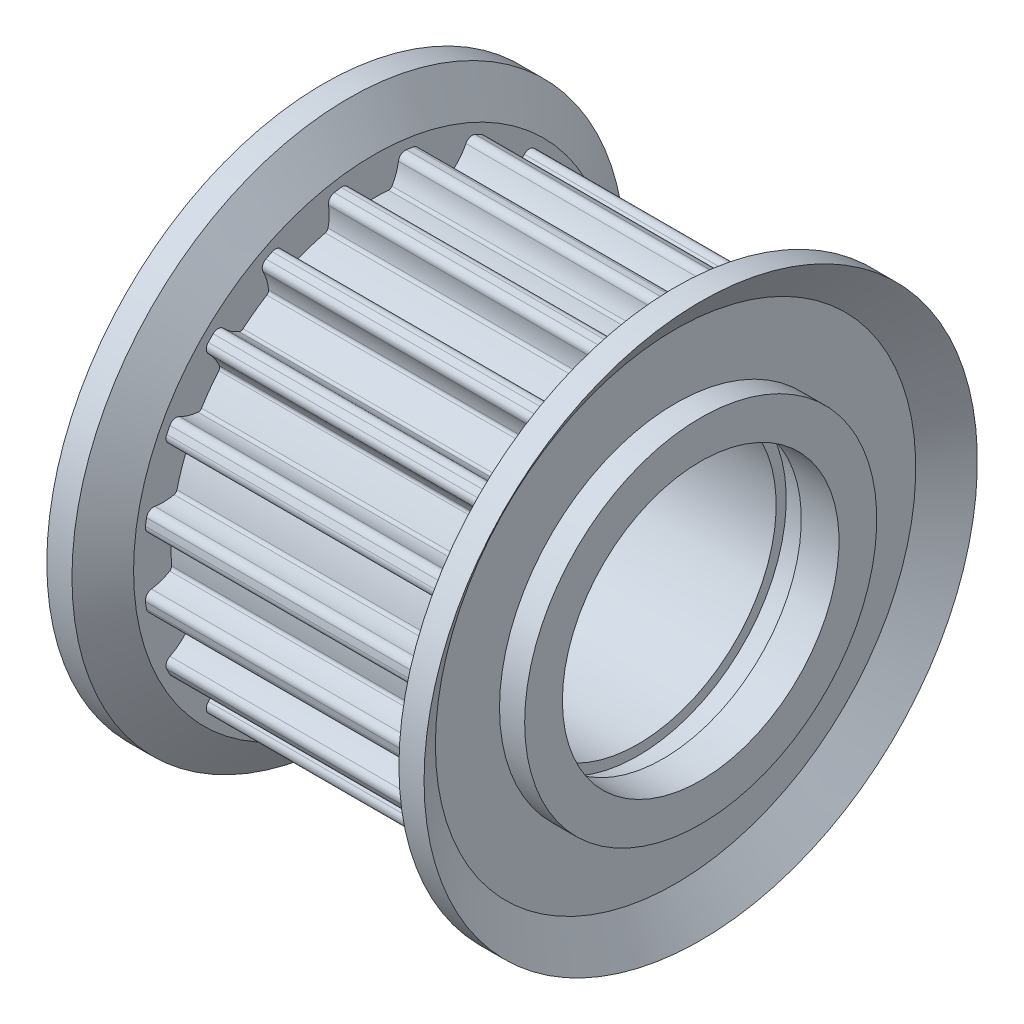
SolidWorks part; units mm, degrees
ref_plane "Front Plane" through (0, 0, 0) normal (0, 0, 1) x (1, 0, 0)
ref_plane "Top Plane" through (0, 0, 0) normal (0, 1, 0) x (1, 0, 0)
ref_plane "Right Plane" through (0, 0, 0) normal (1, 0, 0) x (0, 0, -1)
ref_plane "Plane1" through (0, 0, 0) normal (0, 0, 1) x (1, 0, 0)
sketch "Sketch1" plane through (0, 0, 0) normal (0, 0, 1) x (1, 0, 0)
  line L0 (-7.5, 4.5) -> (-5, 4.5)
  line L1 (-5, 4.5) -> (-5, 5.5)
  line L2 (-5, 5.5) -> (5, 5.5)
  line L3 (5, 5.5) -> (5, 5.9)
  line L4 (5, 5.9) -> (6, 5.9)
  line L5 (6, 5.9) -> (6, 5.5)
  line L6 (6, 5.5) -> (7.5, 5.5)
  line L7 (7.5, 5.5) -> (7.5, 7)
  line L8 (7.5, 7) -> (6.5, 7)
  line L9 (6.5, 7) -> (6.5, 9.55)
  line L10 (6.5, 9.55) -> (7.5, 11)
  line L11 (7.5, 11) -> (6.5, 11)
  line L12 (6.5, 11) -> (5.5, 9.55)
  line L13 (5.5, 9.55) -> (5.5, 9.17)
  line L14 (5.5, 9.17) -> (-5.5, 9.17)
  line L15 (-5.5, 9.17) -> (-5.5, 9.55)
  line L16 (-5.5, 9.55) -> (-6.5, 11)
  line L17 (-6.5, 11) -> (-7.5, 11)
  line L18 (-7.5, 11) -> (-6.5, 9.55)
  line L19 (-6.5, 9.55) -> (-6.5, 7)
  line L20 (-6.5, 7) -> (-7.5, 7)
  line L21 (-7.5, 7) -> (-7.5, 4.5)
  line L22 (20, 0) -> (-20, 0) construction
revolve "Revolve1" add sketch "Sketch1" angle 360 about L22 reverse direction yes
ref_plane "Plane2" through (5.5, 0, 0) normal (1, 0, 0) x (0, 0, -1)
sketch "Sketch2" plane through (5.5, 0, 0) normal (1, 0, 0) x (0, 0, -1)
  line L0 (1.2972, 9.0778) -> (1.2972, 9.8469)
  line L1 (-1.2972, 9.8469) -> (-1.2972, 9.0778)
  arc A0 (-1.2972, 9.0778) -> (-0.9803, 8.84) centre (-1.2575, 8.8006) cw
  arc A1 (-0.9803, 8.84) -> (-0.7246, 8.112) centre (0.975, 9.118) ccw
  arc A2 (-0.7246, 8.112) -> (-0.5846, 8.0388) centre (-0.5955, 8.1884) ccw
  arc A3 (-0.5846, 8.0388) -> (0.5846, 8.0388) centre (0, 0) cw
  arc A4 (0.5846, 8.0388) -> (0.7246, 8.112) centre (0.5955, 8.1884) ccw
  arc A5 (0.7246, 8.112) -> (0.9803, 8.84) centre (-0.975, 9.118) ccw
  arc A6 (0.9803, 8.84) -> (1.2972, 9.0778) centre (1.2575, 8.8006) cw
  arc A7 (1.2972, 9.8469) -> (-1.2972, 9.8469) centre (0, 0) ccw
extrude "Cut-Extrude1" cut sketch "Sketch2" against normal blind 11
ref_plane "Plane3" through (5.5, 0, 0) normal (1, 0, 0) x (0, 0, -1)
sketch "Sketch3" plane through (5.5, 0, 0) normal (1, 0, 0) x (0, 0, -1)
  line L0 (4.0389, 8.2326) -> (4.2765, 8.9641)
  line L1 (1.8092, 9.7658) -> (1.5715, 9.0343)
  arc A0 (1.5715, 9.0343) -> (1.7994, 8.7103) centre (1.5235, 8.7585) cw
  arc A1 (1.7994, 8.7103) -> (1.8176, 7.9388) centre (3.7449, 8.3705) ccw
  arc A2 (1.8176, 7.9388) -> (1.9281, 7.826) centre (1.964, 7.9716) ccw
  arc A3 (1.9281, 7.826) -> (3.0401, 7.4647) centre (0, 0) cw
  arc A4 (3.0401, 7.4647) -> (3.1958, 7.491) centre (3.0967, 7.6036) ccw
  arc A5 (3.1958, 7.491) -> (3.6641, 8.1044) centre (1.8903, 8.973) ccw
  arc A6 (3.6641, 8.1044) -> (4.0389, 8.2326) centre (3.9155, 7.9813) cw
  arc A7 (4.2765, 8.9641) -> (1.8092, 9.7658) centre (0, 0) ccw
extrude "Cut-Extrude2" cut sketch "Sketch3" against normal blind 11
ref_plane "Plane4" through (5.5, 0, 0) normal (1, 0, 0) x (0, 0, -1)
sketch "Sketch4" plane through (5.5, 0, 0) normal (1, 0, 0) x (0, 0, -1)
  line L0 (6.3852, 6.5816) -> (6.8373, 7.2039)
  line L1 (4.7385, 8.7288) -> (4.2864, 8.1065)
  arc A0 (4.2864, 8.1065) -> (4.4029, 7.728) centre (4.1555, 7.859) cw
  arc A1 (4.4029, 7.728) -> (4.1819, 6.9886) centre (6.1482, 6.8035) ccw
  arc A2 (4.1819, 6.9886) -> (4.2521, 6.8471) centre (4.3313, 6.9745) ccw
  arc A3 (4.2521, 6.8471) -> (5.198, 6.1599) centre (0, 0) cw
  arc A4 (5.198, 6.1599) -> (5.3543, 6.1368) centre (5.2948, 6.2745) ccw
  arc A5 (5.3543, 6.1368) -> (5.9891, 6.5755) centre (4.5706, 7.9497) ccw
  arc A6 (5.9891, 6.5755) -> (6.3852, 6.5816) centre (6.1902, 6.3807) cw
  arc A7 (6.8373, 7.2039) -> (4.7385, 8.7288) centre (0, 0) ccw
extrude "Cut-Extrude3" cut sketch "Sketch4" against normal blind 11
ref_plane "Plane5" through (5.5, 0, 0) normal (1, 0, 0) x (0, 0, -1)
sketch "Sketch5" plane through (5.5, 0, 0) normal (1, 0, 0) x (0, 0, -1)
  line L0 (8.1065, 4.2864) -> (8.7288, 4.7385)
  line L1 (7.2039, 6.8373) -> (6.5816, 6.3852)
  arc A0 (6.5816, 6.3852) -> (6.5755, 5.9891) centre (6.3807, 6.1902) cw
  arc A1 (6.5755, 5.9891) -> (6.1368, 5.3543) centre (7.9497, 4.5706) ccw
  arc A2 (6.1368, 5.3543) -> (6.1599, 5.198) centre (6.2745, 5.2948) ccw
  arc A3 (6.1599, 5.198) -> (6.8471, 4.2521) centre (0, 0) cw
  arc A4 (6.8471, 4.2521) -> (6.9886, 4.1819) centre (6.9745, 4.3313) ccw
  arc A5 (6.9886, 4.1819) -> (7.728, 4.4029) centre (6.8035, 6.1482) ccw
  arc A6 (7.728, 4.4029) -> (8.1065, 4.2864) centre (7.859, 4.1555) cw
  arc A7 (8.7288, 4.7385) -> (7.2039, 6.8373) centre (0, 0) ccw
extrude "Cut-Extrude4" cut sketch "Sketch5" against normal blind 11
ref_plane "Plane6" through (5.5, 0, 0) normal (1, 0, 0) x (0, 0, -1)
sketch "Sketch6" plane through (5.5, 0, 0) normal (1, 0, 0) x (0, 0, -1)
  line L0 (9.0343, 1.5715) -> (9.7658, 1.8092)
  line L1 (8.9641, 4.2765) -> (8.2326, 4.0389)
  arc A0 (8.2326, 4.0389) -> (8.1044, 3.6641) centre (7.9813, 3.9155) cw
  arc A1 (8.1044, 3.6641) -> (7.491, 3.1958) centre (8.973, 1.8903) ccw
  arc A2 (7.491, 3.1958) -> (7.4647, 3.0401) centre (7.6036, 3.0967) ccw
  arc A3 (7.4647, 3.0401) -> (7.826, 1.9281) centre (0, 0) cw
  arc A4 (7.826, 1.9281) -> (7.9388, 1.8176) centre (7.9716, 1.964) ccw
  arc A5 (7.9388, 1.8176) -> (8.7103, 1.7994) centre (8.3705, 3.7449) ccw
  arc A6 (8.7103, 1.7994) -> (9.0343, 1.5715) centre (8.7585, 1.5235) cw
  arc A7 (9.7658, 1.8092) -> (8.9641, 4.2765) centre (0, 0) ccw
extrude "Cut-Extrude5" cut sketch "Sketch6" against normal blind 11
ref_plane "Plane7" through (5.5, 0, 0) normal (1, 0, 0) x (0, 0, -1)
sketch "Sketch7" plane through (5.5, 0, 0) normal (1, 0, 0) x (0, 0, -1)
  line L0 (9.0778, -1.2972) -> (9.8469, -1.2972)
  line L1 (9.8469, 1.2972) -> (9.0778, 1.2972)
  arc A0 (9.0778, 1.2972) -> (8.84, 0.9803) centre (8.8006, 1.2575) cw
  arc A1 (8.84, 0.9803) -> (8.112, 0.7246) centre (9.118, -0.975) ccw
  arc A2 (8.112, 0.7246) -> (8.0388, 0.5846) centre (8.1884, 0.5955) ccw
  arc A3 (8.0388, 0.5846) -> (8.0388, -0.5846) centre (0, 0) cw
  arc A4 (8.0388, -0.5846) -> (8.112, -0.7246) centre (8.1884, -0.5955) ccw
  arc A5 (8.112, -0.7246) -> (8.84, -0.9803) centre (9.118, 0.975) ccw
  arc A6 (8.84, -0.9803) -> (9.0778, -1.2972) centre (8.8006, -1.2575) cw
  arc A7 (9.8469, -1.2972) -> (9.8469, 1.2972) centre (0, 0) ccw
extrude "Cut-Extrude6" cut sketch "Sketch7" against normal blind 11
ref_plane "Plane8" through (5.5, 0, 0) normal (1, 0, 0) x (0, 0, -1)
sketch "Sketch8" plane through (5.5, 0, 0) normal (1, 0, 0) x (0, 0, -1)
  line L0 (8.2326, -4.0389) -> (8.9641, -4.2765)
  line L1 (9.7658, -1.8092) -> (9.0343, -1.5715)
  arc A0 (9.0343, -1.5715) -> (8.7103, -1.7994) centre (8.7585, -1.5235) cw
  arc A1 (8.7103, -1.7994) -> (7.9388, -1.8176) centre (8.3705, -3.7449) ccw
  arc A2 (7.9388, -1.8176) -> (7.826, -1.9281) centre (7.9716, -1.964) ccw
  arc A3 (7.826, -1.9281) -> (7.4647, -3.0401) centre (0, 0) cw
  arc A4 (7.4647, -3.0401) -> (7.491, -3.1958) centre (7.6036, -3.0967) ccw
  arc A5 (7.491, -3.1958) -> (8.1044, -3.6641) centre (8.973, -1.8903) ccw
  arc A6 (8.1044, -3.6641) -> (8.2326, -4.0389) centre (7.9813, -3.9155) cw
  arc A7 (8.9641, -4.2765) -> (9.7658, -1.8092) centre (0, 0) ccw
extrude "Cut-Extrude7" cut sketch "Sketch8" against normal blind 11
ref_plane "Plane9" through (5.5, 0, 0) normal (1, 0, 0) x (0, 0, -1)
sketch "Sketch9" plane through (5.5, 0, 0) normal (1, 0, 0) x (0, 0, -1)
  line L0 (6.5816, -6.3852) -> (7.2039, -6.8373)
  line L1 (8.7288, -4.7385) -> (8.1065, -4.2864)
  arc A0 (8.1065, -4.2864) -> (7.728, -4.4029) centre (7.859, -4.1555) cw
  arc A1 (7.728, -4.4029) -> (6.9886, -4.1819) centre (6.8035, -6.1482) ccw
  arc A2 (6.9886, -4.1819) -> (6.8471, -4.2521) centre (6.9745, -4.3313) ccw
  arc A3 (6.8471, -4.2521) -> (6.1599, -5.198) centre (0, 0) cw
  arc A4 (6.1599, -5.198) -> (6.1368, -5.3543) centre (6.2745, -5.2948) ccw
  arc A5 (6.1368, -5.3543) -> (6.5755, -5.9891) centre (7.9497, -4.5706) ccw
  arc A6 (6.5755, -5.9891) -> (6.5816, -6.3852) centre (6.3807, -6.1902) cw
  arc A7 (7.2039, -6.8373) -> (8.7288, -4.7385) centre (0, 0) ccw
extrude "Cut-Extrude8" cut sketch "Sketch9" against normal blind 11
ref_plane "Plane10" through (5.5, 0, 0) normal (1, 0, 0) x (0, 0, -1)
sketch "Sketch10" plane through (5.5, 0, 0) normal (1, 0, 0) x (0, 0, -1)
  line L0 (4.2864, -8.1065) -> (4.7385, -8.7288)
  line L1 (6.8373, -7.2039) -> (6.3852, -6.5816)
  arc A0 (6.3852, -6.5816) -> (5.9891, -6.5755) centre (6.1902, -6.3807) cw
  arc A1 (5.9891, -6.5755) -> (5.3543, -6.1368) centre (4.5706, -7.9497) ccw
  arc A2 (5.3543, -6.1368) -> (5.198, -6.1599) centre (5.2948, -6.2745) ccw
  arc A3 (5.198, -6.1599) -> (4.2521, -6.8471) centre (0, 0) cw
  arc A4 (4.2521, -6.8471) -> (4.1819, -6.9886) centre (4.3313, -6.9745) ccw
  arc A5 (4.1819, -6.9886) -> (4.4029, -7.728) centre (6.1482, -6.8035) ccw
  arc A6 (4.4029, -7.728) -> (4.2864, -8.1065) centre (4.1555, -7.859) cw
  arc A7 (4.7385, -8.7288) -> (6.8373, -7.2039) centre (0, 0) ccw
extrude "Cut-Extrude9" cut sketch "Sketch10" against normal blind 11
ref_plane "Plane11" through (5.5, 0, 0) normal (1, 0, 0) x (0, 0, -1)
sketch "Sketch11" plane through (5.5, 0, 0) normal (1, 0, 0) x (0, 0, -1)
  line L0 (1.5715, -9.0343) -> (1.8092, -9.7658)
  line L1 (4.2765, -8.9641) -> (4.0389, -8.2326)
  arc A0 (4.0389, -8.2326) -> (3.6641, -8.1044) centre (3.9155, -7.9813) cw
  arc A1 (3.6641, -8.1044) -> (3.1958, -7.491) centre (1.8903, -8.973) ccw
  arc A2 (3.1958, -7.491) -> (3.0401, -7.4647) centre (3.0967, -7.6036) ccw
  arc A3 (3.0401, -7.4647) -> (1.9281, -7.826) centre (0, 0) cw
  arc A4 (1.9281, -7.826) -> (1.8176, -7.9388) centre (1.964, -7.9716) ccw
  arc A5 (1.8176, -7.9388) -> (1.7994, -8.7103) centre (3.7449, -8.3705) ccw
  arc A6 (1.7994, -8.7103) -> (1.5715, -9.0343) centre (1.5235, -8.7585) cw
  arc A7 (1.8092, -9.7658) -> (4.2765, -8.9641) centre (0, 0) ccw
extrude "Cut-Extrude10" cut sketch "Sketch11" against normal blind 11
ref_plane "Plane12" through (5.5, 0, 0) normal (1, 0, 0) x (0, 0, -1)
sketch "Sketch12" plane through (5.5, 0, 0) normal (1, 0, 0) x (0, 0, -1)
  line L0 (-1.2972, -9.0778) -> (-1.2972, -9.8469)
  line L1 (1.2972, -9.8469) -> (1.2972, -9.0778)
  arc A0 (1.2972, -9.0778) -> (0.9803, -8.84) centre (1.2575, -8.8006) cw
  arc A1 (0.9803, -8.84) -> (0.7246, -8.112) centre (-0.975, -9.118) ccw
  arc A2 (0.7246, -8.112) -> (0.5846, -8.0388) centre (0.5955, -8.1884) ccw
  arc A3 (0.5846, -8.0388) -> (-0.5846, -8.0388) centre (0, 0) cw
  arc A4 (-0.5846, -8.0388) -> (-0.7246, -8.112) centre (-0.5955, -8.1884) ccw
  arc A5 (-0.7246, -8.112) -> (-0.9803, -8.84) centre (0.975, -9.118) ccw
  arc A6 (-0.9803, -8.84) -> (-1.2972, -9.0778) centre (-1.2575, -8.8006) cw
  arc A7 (-1.2972, -9.8469) -> (1.2972, -9.8469) centre (0, 0) ccw
extrude "Cut-Extrude11" cut sketch "Sketch12" against normal blind 11
ref_plane "Plane13" through (5.5, 0, 0) normal (1, 0, 0) x (0, 0, -1)
sketch "Sketch13" plane through (5.5, 0, 0) normal (1, 0, 0) x (0, 0, -1)
  line L0 (-4.0389, -8.2326) -> (-4.2765, -8.9641)
  line L1 (-1.8092, -9.7658) -> (-1.5715, -9.0343)
  arc A0 (-1.5715, -9.0343) -> (-1.7994, -8.7103) centre (-1.5235, -8.7585) cw
  arc A1 (-1.7994, -8.7103) -> (-1.8176, -7.9388) centre (-3.7449, -8.3705) ccw
  arc A2 (-1.8176, -7.9388) -> (-1.9281, -7.826) centre (-1.964, -7.9716) ccw
  arc A3 (-1.9281, -7.826) -> (-3.0401, -7.4647) centre (0, 0) cw
  arc A4 (-3.0401, -7.4647) -> (-3.1958, -7.491) centre (-3.0967, -7.6036) ccw
  arc A5 (-3.1958, -7.491) -> (-3.6641, -8.1044) centre (-1.8903, -8.973) ccw
  arc A6 (-3.6641, -8.1044) -> (-4.0389, -8.2326) centre (-3.9155, -7.9813) cw
  arc A7 (-4.2765, -8.9641) -> (-1.8092, -9.7658) centre (0, 0) ccw
extrude "Cut-Extrude12" cut sketch "Sketch13" against normal blind 11
ref_plane "Plane14" through (5.5, 0, 0) normal (1, 0, 0) x (0, 0, -1)
sketch "Sketch14" plane through (5.5, 0, 0) normal (1, 0, 0) x (0, 0, -1)
  line L0 (-6.3852, -6.5816) -> (-6.8373, -7.2039)
  line L1 (-4.7385, -8.7288) -> (-4.2864, -8.1065)
  arc A0 (-4.2864, -8.1065) -> (-4.4029, -7.728) centre (-4.1555, -7.859) cw
  arc A1 (-4.4029, -7.728) -> (-4.1819, -6.9886) centre (-6.1482, -6.8035) ccw
  arc A2 (-4.1819, -6.9886) -> (-4.2521, -6.8471) centre (-4.3313, -6.9745) ccw
  arc A3 (-4.2521, -6.8471) -> (-5.198, -6.1599) centre (0, 0) cw
  arc A4 (-5.198, -6.1599) -> (-5.3543, -6.1368) centre (-5.2948, -6.2745) ccw
  arc A5 (-5.3543, -6.1368) -> (-5.9891, -6.5755) centre (-4.5706, -7.9497) ccw
  arc A6 (-5.9891, -6.5755) -> (-6.3852, -6.5816) centre (-6.1902, -6.3807) cw
  arc A7 (-6.8373, -7.2039) -> (-4.7385, -8.7288) centre (0, 0) ccw
extrude "Cut-Extrude13" cut sketch "Sketch14" against normal blind 11
ref_plane "Plane15" through (5.5, 0, 0) normal (1, 0, 0) x (0, 0, -1)
sketch "Sketch15" plane through (5.5, 0, 0) normal (1, 0, 0) x (0, 0, -1)
  line L0 (-8.1065, -4.2864) -> (-8.7288, -4.7385)
  line L1 (-7.2039, -6.8373) -> (-6.5816, -6.3852)
  arc A0 (-6.5816, -6.3852) -> (-6.5755, -5.9891) centre (-6.3807, -6.1902) cw
  arc A1 (-6.5755, -5.9891) -> (-6.1368, -5.3543) centre (-7.9497, -4.5706) ccw
  arc A2 (-6.1368, -5.3543) -> (-6.1599, -5.198) centre (-6.2745, -5.2948) ccw
  arc A3 (-6.1599, -5.198) -> (-6.8471, -4.2521) centre (0, 0) cw
  arc A4 (-6.8471, -4.2521) -> (-6.9886, -4.1819) centre (-6.9745, -4.3313) ccw
  arc A5 (-6.9886, -4.1819) -> (-7.728, -4.4029) centre (-6.8035, -6.1482) ccw
  arc A6 (-7.728, -4.4029) -> (-8.1065, -4.2864) centre (-7.859, -4.1555) cw
  arc A7 (-8.7288, -4.7385) -> (-7.2039, -6.8373) centre (0, 0) ccw
extrude "Cut-Extrude14" cut sketch "Sketch15" against normal blind 11
ref_plane "Plane16" through (5.5, 0, 0) normal (1, 0, 0) x (0, 0, -1)
sketch "Sketch16" plane through (5.5, 0, 0) normal (1, 0, 0) x (0, 0, -1)
  line L0 (-9.0343, -1.5715) -> (-9.7658, -1.8092)
  line L1 (-8.9641, -4.2765) -> (-8.2326, -4.0389)
  arc A0 (-8.2326, -4.0389) -> (-8.1044, -3.6641) centre (-7.9813, -3.9155) cw
  arc A1 (-8.1044, -3.6641) -> (-7.491, -3.1958) centre (-8.973, -1.8903) ccw
  arc A2 (-7.491, -3.1958) -> (-7.4647, -3.0401) centre (-7.6036, -3.0967) ccw
  arc A3 (-7.4647, -3.0401) -> (-7.826, -1.9281) centre (0, 0) cw
  arc A4 (-7.826, -1.9281) -> (-7.9388, -1.8176) centre (-7.9716, -1.964) ccw
  arc A5 (-7.9388, -1.8176) -> (-8.7103, -1.7994) centre (-8.3705, -3.7449) ccw
  arc A6 (-8.7103, -1.7994) -> (-9.0343, -1.5715) centre (-8.7585, -1.5235) cw
  arc A7 (-9.7658, -1.8092) -> (-8.9641, -4.2765) centre (0, 0) ccw
extrude "Cut-Extrude15" cut sketch "Sketch16" against normal blind 11
ref_plane "Plane17" through (5.5, 0, 0) normal (1, 0, 0) x (0, 0, -1)
sketch "Sketch17" plane through (5.5, 0, 0) normal (1, 0, 0) x (0, 0, -1)
  line L0 (-9.0778, 1.2972) -> (-9.8469, 1.2972)
  line L1 (-9.8469, -1.2972) -> (-9.0778, -1.2972)
  arc A0 (-9.0778, -1.2972) -> (-8.84, -0.9803) centre (-8.8006, -1.2575) cw
  arc A1 (-8.84, -0.9803) -> (-8.112, -0.7246) centre (-9.118, 0.975) ccw
  arc A2 (-8.112, -0.7246) -> (-8.0388, -0.5846) centre (-8.1884, -0.5955) ccw
  arc A3 (-8.0388, -0.5846) -> (-8.0388, 0.5846) centre (0, 0) cw
  arc A4 (-8.0388, 0.5846) -> (-8.112, 0.7246) centre (-8.1884, 0.5955) ccw
  arc A5 (-8.112, 0.7246) -> (-8.84, 0.9803) centre (-9.118, -0.975) ccw
  arc A6 (-8.84, 0.9803) -> (-9.0778, 1.2972) centre (-8.8006, 1.2575) cw
  arc A7 (-9.8469, 1.2972) -> (-9.8469, -1.2972) centre (0, 0) ccw
extrude "Cut-Extrude16" cut sketch "Sketch17" against normal blind 11
ref_plane "Plane18" through (5.5, 0, 0) normal (1, 0, 0) x (0, 0, -1)
sketch "Sketch18" plane through (5.5, 0, 0) normal (1, 0, 0) x (0, 0, -1)
  line L0 (-8.2326, 4.0389) -> (-8.9641, 4.2765)
  line L1 (-9.7658, 1.8092) -> (-9.0343, 1.5715)
  arc A0 (-9.0343, 1.5715) -> (-8.7103, 1.7994) centre (-8.7585, 1.5235) cw
  arc A1 (-8.7103, 1.7994) -> (-7.9388, 1.8176) centre (-8.3705, 3.7449) ccw
  arc A2 (-7.9388, 1.8176) -> (-7.826, 1.9281) centre (-7.9716, 1.964) ccw
  arc A3 (-7.826, 1.9281) -> (-7.4647, 3.0401) centre (0, 0) cw
  arc A4 (-7.4647, 3.0401) -> (-7.491, 3.1958) centre (-7.6036, 3.0967) ccw
  arc A5 (-7.491, 3.1958) -> (-8.1044, 3.6641) centre (-8.973, 1.8903) ccw
  arc A6 (-8.1044, 3.6641) -> (-8.2326, 4.0389) centre (-7.9813, 3.9155) cw
  arc A7 (-8.9641, 4.2765) -> (-9.7658, 1.8092) centre (0, 0) ccw
extrude "Cut-Extrude17" cut sketch "Sketch18" against normal blind 11
ref_plane "Plane19" through (5.5, 0, 0) normal (1, 0, 0) x (0, 0, -1)
sketch "Sketch19" plane through (5.5, 0, 0) normal (1, 0, 0) x (0, 0, -1)
  line L0 (-6.5816, 6.3852) -> (-7.2039, 6.8373)
  line L1 (-8.7288, 4.7385) -> (-8.1065, 4.2864)
  arc A0 (-8.1065, 4.2864) -> (-7.728, 4.4029) centre (-7.859, 4.1555) cw
  arc A1 (-7.728, 4.4029) -> (-6.9886, 4.1819) centre (-6.8035, 6.1482) ccw
  arc A2 (-6.9886, 4.1819) -> (-6.8471, 4.2521) centre (-6.9745, 4.3313) ccw
  arc A3 (-6.8471, 4.2521) -> (-6.1599, 5.198) centre (0, 0) cw
  arc A4 (-6.1599, 5.198) -> (-6.1368, 5.3543) centre (-6.2745, 5.2948) ccw
  arc A5 (-6.1368, 5.3543) -> (-6.5755, 5.9891) centre (-7.9497, 4.5706) ccw
  arc A6 (-6.5755, 5.9891) -> (-6.5816, 6.3852) centre (-6.3807, 6.1902) cw
  arc A7 (-7.2039, 6.8373) -> (-8.7288, 4.7385) centre (0, 0) ccw
extrude "Cut-Extrude18" cut sketch "Sketch19" against normal blind 11
ref_plane "Plane20" through (5.5, 0, 0) normal (1, 0, 0) x (0, 0, -1)
sketch "Sketch20" plane through (5.5, 0, 0) normal (1, 0, 0) x (0, 0, -1)
  line L0 (-4.2864, 8.1065) -> (-4.7385, 8.7288)
  line L1 (-6.8373, 7.2039) -> (-6.3852, 6.5816)
  arc A0 (-6.3852, 6.5816) -> (-5.9891, 6.5755) centre (-6.1902, 6.3807) cw
  arc A1 (-5.9891, 6.5755) -> (-5.3543, 6.1368) centre (-4.5706, 7.9497) ccw
  arc A2 (-5.3543, 6.1368) -> (-5.198, 6.1599) centre (-5.2948, 6.2745) ccw
  arc A3 (-5.198, 6.1599) -> (-4.2521, 6.8471) centre (0, 0) cw
  arc A4 (-4.2521, 6.8471) -> (-4.1819, 6.9886) centre (-4.3313, 6.9745) ccw
  arc A5 (-4.1819, 6.9886) -> (-4.4029, 7.728) centre (-6.1482, 6.8035) ccw
  arc A6 (-4.4029, 7.728) -> (-4.2864, 8.1065) centre (-4.1555, 7.859) cw
  arc A7 (-4.7385, 8.7288) -> (-6.8373, 7.2039) centre (0, 0) ccw
extrude "Cut-Extrude19" cut sketch "Sketch20" against normal blind 11
ref_plane "Plane21" through (5.5, 0, 0) normal (1, 0, 0) x (0, 0, -1)
sketch "Sketch21" plane through (5.5, 0, 0) normal (1, 0, 0) x (0, 0, -1)
  line L0 (-1.5715, 9.0343) -> (-1.8092, 9.7658)
  line L1 (-4.2765, 8.9641) -> (-4.0389, 8.2326)
  arc A0 (-4.0389, 8.2326) -> (-3.6641, 8.1044) centre (-3.9155, 7.9813) cw
  arc A1 (-3.6641, 8.1044) -> (-3.1958, 7.491) centre (-1.8903, 8.973) ccw
  arc A2 (-3.1958, 7.491) -> (-3.0401, 7.4647) centre (-3.0967, 7.6036) ccw
  arc A3 (-3.0401, 7.4647) -> (-1.9281, 7.826) centre (0, 0) cw
  arc A4 (-1.9281, 7.826) -> (-1.8176, 7.9388) centre (-1.964, 7.9716) ccw
  arc A5 (-1.8176, 7.9388) -> (-1.7994, 8.7103) centre (-3.7449, 8.3705) ccw
  arc A6 (-1.7994, 8.7103) -> (-1.5715, 9.0343) centre (-1.5235, 8.7585) cw
  arc A7 (-1.8092, 9.7658) -> (-4.2765, 8.9641) centre (0, 0) ccw
extrude "Cut-Extrude20" cut sketch "Sketch21" against normal blind 11
sketch "Sketch23" plane through (-7.5, 0, 0) normal (-1, 0, 0) x (0, 0, 1)
  circle A0 centre (0, 0) radius 5
  dimension "D1" = 10
extrude "Cut-Extrude21" cut sketch "Sketch23" against normal through all
sketch "Sketch24" plane through (0, 0, 0) normal (0, 1, 0) x (1, 0, 0)
  circle A0 centre (0, 0) radius 0.75
  dimension "D1" = 1.5
extrude "Cut-Extrude22" cut sketch "Sketch24" against normal through all
